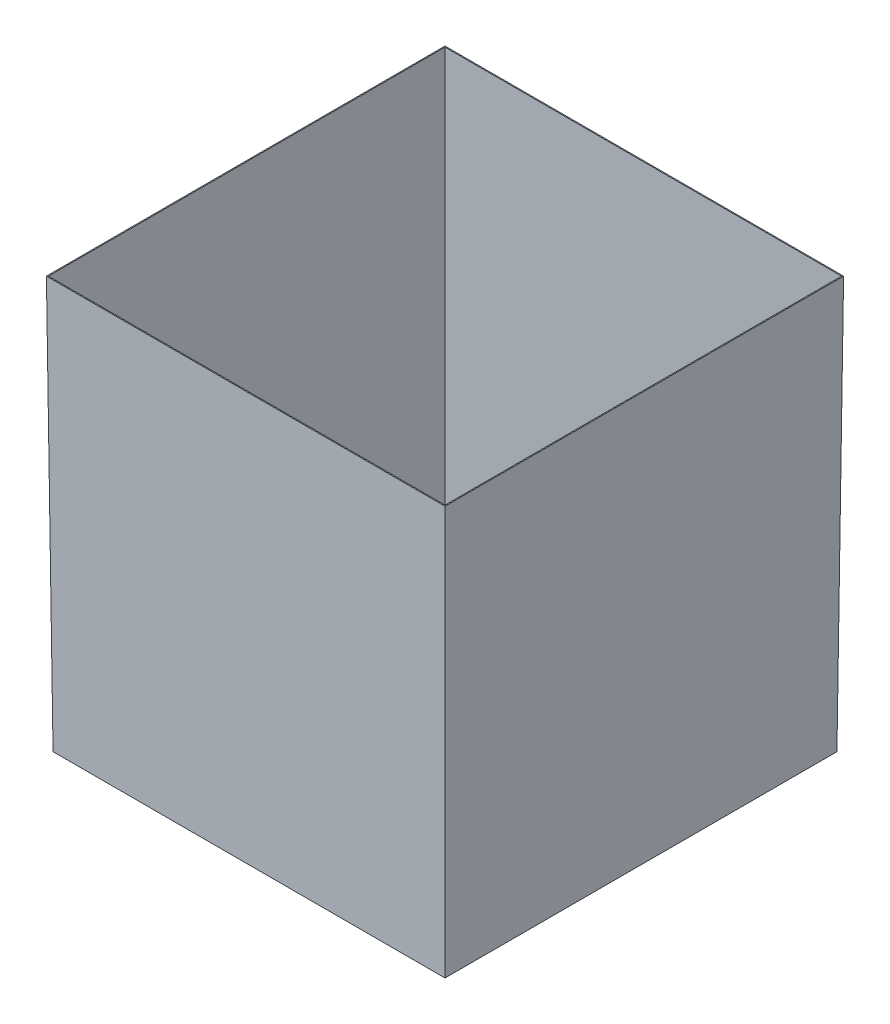
SolidWorks part; units mm, degrees
material "09Г2С ГОСТ 4543-71"
ref_plane "Спереди" through (0, 0, 0) normal (0, 0, 1) x (1, 0, 0)
ref_plane "Сверху" through (0, 0, 0) normal (0, 1, 0) x (1, 0, 0)
ref_plane "Справа" through (0, 0, 0) normal (1, 0, 0) x (0, 0, -1)
other "Configuration Table"
sketch "Эскиз1" plane through (0, 0, 0) normal (0, 1, 0) x (1, 0, 0)
  line L1 (-295, -295) -> (295, -295)
  line L2 (-295, -295) -> (-295, 295)
  line L3 (-295, 295) -> (295, 295)
  line L4 (295, -295) -> (295, 295)
ref_plane "Плоскость1" through (0, 620, 0) normal (0, 1, 0) x (1, 0, 0)
sketch "Эскиз2" plane through (0, 620, 0) normal (0, 1, 0) x (1, 0, 0)
  line L1 (-300, -300) -> (300, -300)
  line L2 (-300, -300) -> (-300, 300)
  line L3 (-300, 300) -> (300, 300)
  line L4 (300, -300) -> (300, 300)
loft "Корпус 590-600, H620" add profiles "Эскиз1", "Эскиз2"
shell "Стенка и дно 1,5 мм" thickness 1.5 removed face at (0, 620, 0)
